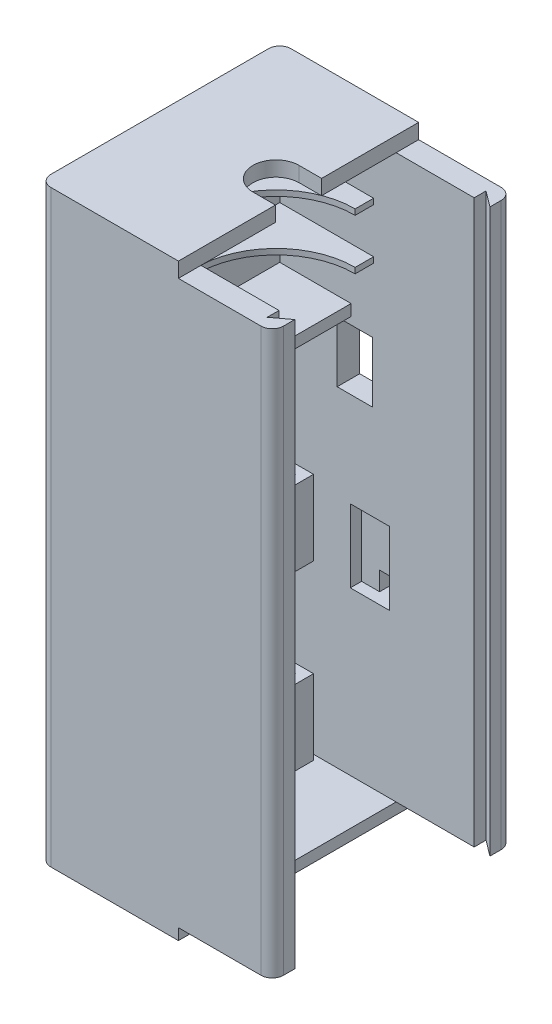
SolidWorks part; units mm, degrees
ref_plane "Alzado" through (0, 0, 0) normal (0, 0, 1) x (1, 0, 0)
ref_plane "Planta" through (0, 0, 0) normal (0, 1, 0) x (1, 0, 0)
ref_plane "Vista lateral" through (0, 0, 0) normal (1, 0, 0) x (0, 0, -1)
sketch "Croquis1" plane through (0, 0, 0) normal (0, 1, 0) x (1, 0, 0)
  line L1 (0, 0) -> (31, 0)
  line L2 (0, 0) -> (0, 32)
  line L3 (0, 32) -> (31, 32)
  line L4 (31, 0) -> (31, 32)
  dimension "D1" = 32
  dimension "D2" = 31
extrude "Saliente-Extruir1" add sketch "Croquis1" along normal blind 78.4
sketch "Croquis2" plane through (31, 0, 0) normal (1, 0, 0) x (0, 0, -1)
  line L1 (3, 76.4) -> (29, 76.4)
  line L2 (3, 1.5) -> (3, 54.5)
  line L3 (3, 1.5) -> (29, 1.5)
  line L4 (16, 78.4) -> (16, 0) construction
  line L5 (0, 78.4) -> (0, 0) construction
  line L6 (0, 78.4) -> (32, 78.4) construction
  line L7 (0, 0) -> (32, 0) construction
  line L9 (3, 56) -> (29, 56) construction
  line L10 (3, 56) -> (29, 56)
  line L11 (3, 54.5) -> (29, 54.5)
  line L24 (29, 76.4) -> (29, 56)
  line L25 (3, 76.4) -> (3, 56)
  line L41 (29, 1.5) -> (29, 54.5)
  point P31 (16, 1.5)
  point P32 (16, 76.4)
  dimension "D1" = 3
  dimension "D2" = 1.5
  dimension "D3" = 53
  dimension "D4" = 1.5
  dimension "D5" = 20.4
extrude "Cortar-Extruir1" cut sketch "Croquis2" against normal offset from surface (26 mm away) 3 from offset 2 up to face at (0, 39.2, -16) offset against normal yes
sketch "Croquis3" plane through (0, 78.4, 0) normal (0, 1, 0) x (1, 0, 0)
  line L0 (0, 32) -> (31, 0) construction
  line L1 (0, 0) -> (31, 32) construction
  line L2 (15.5, 16) -> (15.5, 32) construction
  line L3 (31, 32) -> (0, 32) construction
  circle A0 centre (15.5, 16) radius 3.075
  dimension "D1" = 6.15
extrude "Cortar-Extruir2" cut sketch "Croquis3" against normal blind 5
sketch "Croquis4" plane through (31, 0, 0) normal (1, 0, 0) x (0, 0, -1)
  line L0 (0, 78.4) -> (32, 78.4) construction
  line L1 (3, 76.9) -> (29, 76.9)
  line L2 (3, 76.9) -> (3, 1.5)
  line L3 (3, 1.5) -> (29, 1.5)
  line L4 (29, 76.9) -> (29, 1.5)
  line L5 (32, 78.4) -> (32, 0) construction
  line L6 (0, 78.4) -> (0, 0) construction
  line L7 (0, 0) -> (32, 0) construction
  dimension "D1" = 1.5
  dimension "D2" = 3
  dimension "D3" = 3
  dimension "D4" = 1.5
extrude "Cortar-Extruir3" cut sketch "Croquis4" against normal blind 2
sketch "Croquis5" plane through (0, 54.5, 0) normal (0, -1, 0) x (1, 0, 0)
  line L0 (0, 0) -> (31, -32) construction
  line L1 (31, 0) -> (0, -32) construction
  line L3 (12.5, -16) -> (15.5, -16) construction
  line L5 (12.5, -29) -> (12.5, -3)
  line L6 (3, -29) -> (29, -29) construction
  line L7 (3, -3) -> (29, -3) construction
  line L10 (12.5, -3) -> (34.7476, -3)
  line L11 (34.7476, -3) -> (34.7476, -29)
  line L12 (34.7476, -29) -> (12.5, -29)
  arc A0 (15.5, -13) -> (15.5, -19) centre (15.5, -16) ccw construction
  dimension "D1" = 6
extrude "Cortar-Extruir4" cut sketch "Croquis5" against normal blind 19
sketch "Croquis6" plane through (0, 54.5, 0) normal (0, -1, 0) x (1, 0, 0)
  line L0 (3, -3) -> (31, -3) construction
  line L1 (3, -29) -> (3, -3) construction
  line L2 (3, -17.1) -> (3, -18.3)
  line L3 (3, -18.3) -> (18.2, -18.3)
  line L4 (26, -16) -> (31, -16) construction
  line L5 (17, -17.1) -> (3, -17.1)
  line L7 (3, -3) -> (12.5, -3) construction
  line L8 (31, 0) -> (31, -32) construction
  line L9 (0, 0) -> (31, -32) construction
  line L10 (31, 0) -> (0, -32) construction
  line L12 (17, -3) -> (18.2, -3)
  line L13 (17, -3) -> (17, -17.1)
  line L15 (18.2, -3) -> (18.2, -18.3)
  circle A1 centre (10, -10) radius 7 construction
  circle A2 centre (15.5, -16) radius 1 construction
  circle A3 centre (15.5, -16) radius 10.5 construction
  dimension "D3" = 14
  dimension "D4" = 2
  dimension "D5" = 21
  dimension "D1" = 1.2
  dimension "D2" = 14.1
ref_axis "Eje1" through (15.5, -7.3463, -16) along (0, 1, 0)
sketch "Croquis11" plane through (0, 76.4, 0) normal (0, -1, 0) x (1, 0, 0)
  line L0 (15.5, -3) -> (15.5, -5.45)
  line L1 (3, -3) -> (31, -3) construction
  line L2 (15.5, -3) -> (3, -3)
  line L3 (3, -3) -> (3, -29)
  line L4 (3, -29) -> (15.5, -29)
  line L5 (3, -29) -> (31, -29) construction
  line L6 (15.5, -29) -> (15.5, -26.55)
  line L7 (0, 0) -> (31, -32) construction
  line L8 (31, 0) -> (0, -32) construction
  arc A0 (15.5, -5.45) -> (15.5, -26.55) centre (15.5, -16) ccw
  circle A1 centre (15.5, -16) radius 3 construction
  dimension "D1" = 21.1
  dimension "D3" = 6
  dimension "D2" = 12.5
extrude "Saliente-Extruir4" add sketch "Croquis11" along normal blind 0.75 from offset 6.75
pattern_linear "MatrizL1" count 2 spacing 6.75 along (0, -1, 0) of "Saliente-Extruir4"
extrude "Saliente-Extruir5" add sketch "Croquis6" along normal blind 10 from offset 10
pattern_linear "MatrizL2" count 2 spacing 23 along (0, -1, 0) of "Saliente-Extruir5"
sketch "Croquis14" plane through (0, 76.4, 0) normal (0, -1, 0) x (1, 0, 0)
  line L1 (18.5, 0) -> (31, 0)
  line L2 (18.5, 0) -> (18.5, -12.925)
  line L3 (18.5, -32) -> (31, -32)
  line L4 (31, 0) -> (31, -32)
  line L5 (15.5, -12.925) -> (18.5, -12.925)
  line L7 (15.5, -12.925) -> (15.5, -19.075)
  line L8 (15.5, -19.075) -> (18.5, -19.075)
  line L9 (18.5, -19.075) -> (18.5, -32)
  line L10 (0, 0) -> (31, 0) construction
  circle A0 centre (15.5, -16) radius 3.075 construction
  circle A1 centre (15.5, -16) radius 3 construction
  dimension "D1" = 6
  dimension "D2" = 3
extrude "Cortar-Extruir8" cut sketch "Croquis14" against normal blind 10
sketch "Croquis15" plane through (0, 1.5, 0) normal (0, 1, 0) x (1, 0, 0)
  line L0 (18.5, 0) -> (18.5, 12.925) construction
  line L1 (18.5, 32) -> (31, 32)
  line L2 (18.5, 32) -> (18.5, 0)
  line L3 (18.5, 0) -> (31, 0)
  line L4 (31, 32) -> (31, 0)
  line L5 (18.5, 32) -> (31, 32) construction
extrude "Cortar-Extruir11" cut sketch "Croquis15" against normal blind 10
sketch "Croquis16" plane through (0, 0, 0) normal (-1, 0, 0) x (0, 0, 1)
  line L0 (-3, 54.5) -> (-29, 54.5) construction
  line L1 (-3, 1.5) -> (-17.1, 1.5)
  line L2 (-3, 1.5) -> (-3, 54.5)
  line L3 (-3, 54.5) -> (-17.1, 54.5)
  line L4 (-17.1, 1.5) -> (-17.1, 54.5)
  line L5 (-17.1, 34.5) -> (-17.1, 44.5) construction
extrude "Cortar-Extruir12" cut sketch "Croquis16" against normal blind 10
sketch "Croquis17" plane through (0, 0, 0) normal (0, -1, 0) x (1, 0, 0)
  line L0 (0, -17.1) -> (2.1, -19.2)
  line L1 (2.1, -19.2) -> (2.1, -0.9)
  line L2 (0, -10.05) -> (7.9822, -10.05) construction
  line L3 (0, -3) -> (0, -17.1)
  line L4 (0, -3) -> (2.1, -0.9)
  line L5 (0, 0) -> (18.5, 0) construction
  point P9 (2.1, -10.05)
  dimension "D1" = 18.3
  dimension "D2" = 45
  dimension "D3" = 10.05
extrude "Cortar-Extruir13" cut sketch "Croquis17" against normal up to surface (54.5 mm away) up to face at (3.3333, 54.5, -16.3667)
sketch "Croquis18" plane through (0, 76.4, 0) normal (0, 1, 0) x (1, 0, 0)
  line L0 (31, 29) -> (28.9, 30.575)
  line L1 (28.9, 30.575) -> (28.9, 29)
  line L3 (28.9, 29) -> (31, 29)
  line L4 (0, 16) -> (33.2746, 16) construction
  line L5 (0, 32) -> (0, 0) construction
  line L6 (28.9, 3) -> (31, 3)
  line L7 (28.9, 1.425) -> (28.9, 3)
  line L8 (31, 3) -> (28.9, 1.425)
  dimension "D1" = 53.13
  dimension "D3" = 29.15
extrude "Cortar-Extruir14" cut sketch "Croquis18" against normal blind 95
sketch "Croquis19" plane through (0, 0, -32) normal (0, 0, -1) x (-1, 0, 0)
  line L0 (-31, 53.525) -> (0, 53.525) construction
  line L1 (-15.35, 53.525) -> (-10.65, 53.525)
  line L2 (-15.35, 53.525) -> (-15.35, 45.475)
  line L3 (-15.35, 45.475) -> (-10.65, 45.475)
  line L4 (-10.65, 53.525) -> (-10.65, 45.475)
  line L5 (-31, 76.4) -> (-31, 1.5) construction
  line L6 (0, 78.4) -> (0, 0) construction
  line L8 (-17.6, 32.85) -> (-12.4, 32.85)
  line L9 (-17.6, 32.85) -> (-17.6, 23.15)
  line L10 (-17.6, 23.15) -> (-12.4, 23.15)
  line L11 (-12.4, 32.85) -> (-12.4, 23.15)
  line L12 (-6.9738, 34.5) -> (-6.9738, 21.5) construction
  line L13 (-3, 34.5) -> (-18.2, 34.5) construction
  line L14 (-3, 21.5) -> (-18.2, 21.5) construction
  line L15 (-12.4, 28) -> (-6.9738, 28) construction
  line L16 (-5.9745, 54.5) -> (-5.9745, 44.5) construction
  line L17 (-3, 54.5) -> (-12.5, 54.5) construction
  line L18 (-3, 44.5) -> (-18.2, 44.5) construction
  line L19 (-10.65, 49.5) -> (-5.9745, 49.5) construction
  point P10 (-15, 32.85)
  point P16 (-13, 53.525)
  dimension "D1" = 8.05
  dimension "D2" = 4.7
  dimension "D3" = 5.2
  dimension "D4" = 9.7
  dimension "D5" = 13
  dimension "D6" = 15
extrude "Cortar-Extruir15" cut sketch "Croquis19" along normal offset from surface (1.5 mm away) 1.5 from surface up to face at (17, 39.075, -32) starting at face at (10.7639, 54.55, -29)
sketch "Croquis21" plane through (0, 0, -32) normal (0, 0, -1) x (-1, 0, 0)
  line L1 (-15.35, 53.525) -> (-10.65, 53.525)
  line L2 (-15.35, 53.525) -> (-15.35, 45.475)
  line L3 (-15.35, 45.475) -> (-10.65, 45.475)
  line L4 (-10.65, 53.525) -> (-10.65, 45.475)
  line L5 (-17.6, 23.15) -> (-14.8, 23.15)
  line L6 (-17.6, 23.15) -> (-17.6, 25.65)
  line L7 (-17.6, 25.65) -> (-14.8, 25.65)
  line L8 (-14.8, 23.15) -> (-14.8, 25.65)
  dimension "D1" = 2.5
  dimension "D2" = 2.8
extrude "Cortar-Extruir16" cut sketch "Croquis21" against normal blind 1.5
fillet "Redondeo1" radius 1.5 4 edges at (0, 39.2, 0) (0, 39.2, -32) (31, 38.95, -32) (31, 38.95, 0)
sketch "Croquis22" plane through (0, 0, -32) normal (0, 0, -1) x (-1, 0, 0)
  line L0 (-15.35, 52.1781) -> (-29.5, 52.1781) construction
  line L1 (-29.5, 76.4) -> (-29.5, 1.5) construction
  line L2 (-15.35, 44.5117) -> (-29.5, 44.5117) construction
  line L3 (-17.5, 22.6086) -> (-29.5, 22.6086) construction
  line L4 (-14.9, 22.6086) -> (-1.5, 22.6086) construction
  line L5 (-1.5, 0) -> (-1.5, 78.4) construction
  line L6 (-15.35, 53.525) -> (-15.35, 45.475) construction
  text T0 "ON  " font "Arial" height in points 10
  text T1 "OFF  " font "Arial" height in points 10
  text T2 "-   " font "Arial" height in points 18
  text T3 "+   " font "Arial" height in points 18
extrude "Cortar-Extruir17" cut sketch "Croquis22" against normal blind 1.5
